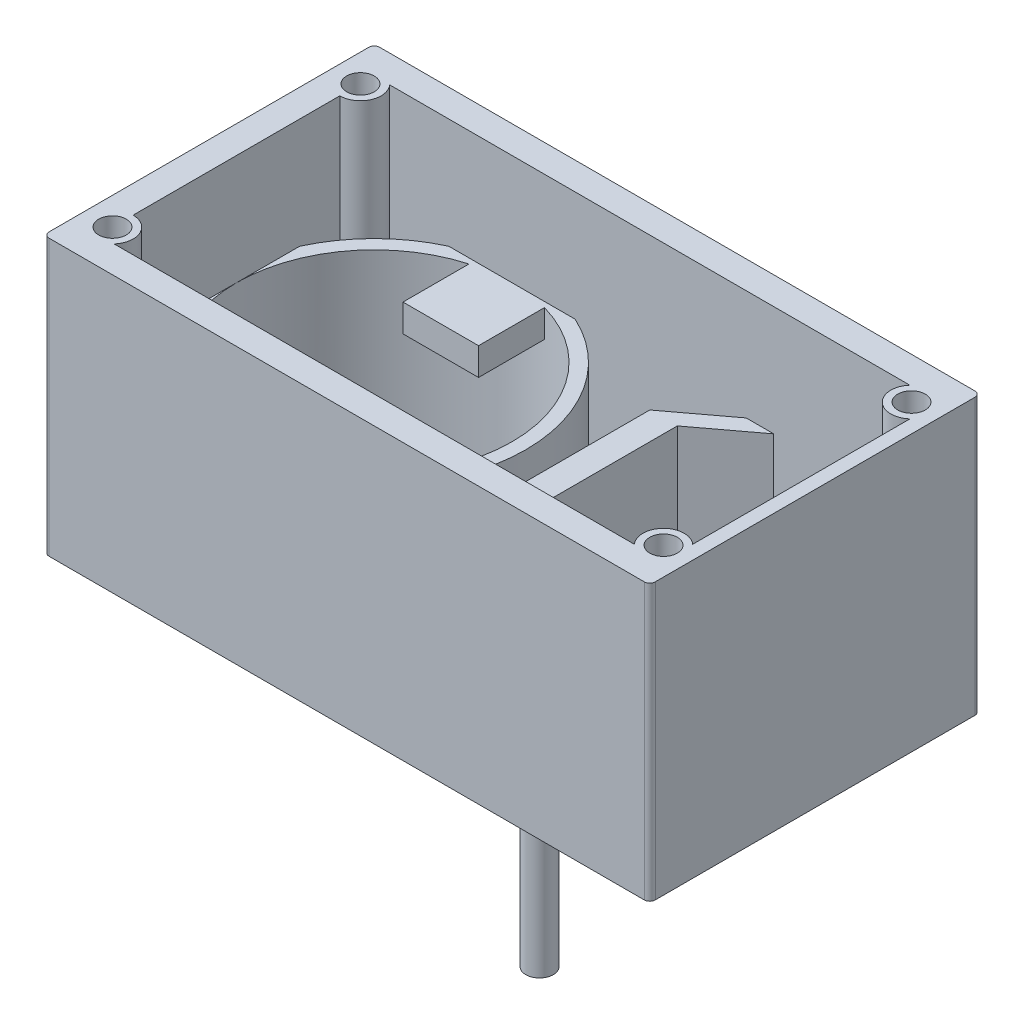
SolidWorks part; units mm, degrees
ref_plane "Front Plane" through (0, 0, 0) normal (0, 0, 1) x (1, 0, 0)
ref_plane "Top Plane" through (0, 0, 0) normal (0, 1, 0) x (1, 0, 0)
ref_plane "Right Plane" through (0, 0, 0) normal (1, 0, 0) x (0, 0, -1)
sketch "Sketch1" plane through (0, 0, 0) normal (0, 1, 0) x (1, 0, 0)
  line L1 (-11, -6) -> (11, -6)
  line L2 (-11, -6) -> (-11, 6)
  line L3 (-11, 6) -> (11, 6)
  line L4 (11, -6) -> (11, 6)
  line L5 (-11, -6) -> (11, 6) construction
  line L6 (-11, 6) -> (11, -6) construction
  point P0 (0, 0)
  dimension "D1" = 12
  dimension "D2" = 22
extrude "Boss-Extrude1" add sketch "Sketch1" along normal blind 10
sketch "Sketch2" plane through (0, 10, 0) normal (0, 1, 0) x (1, 0, 0)
  line L0 (11, 6) -> (-11, 6) construction
  line L1 (10.5, -5) -> (-10, -5)
  line L2 (10.5, -5) -> (10.5, 5)
  line L3 (10.5, 5) -> (-10, 5)
  line L4 (-10, -5) -> (-10, 5)
  line L5 (10.5, -5) -> (-10, 5) construction
  line L6 (10.5, 5) -> (-10, -5) construction
  line L7 (11, -6) -> (11, 6) construction
  point P0 (0.25, 0)
  dimension "D1" = 20.5
  dimension "D2" = 10
  dimension "D3" = 1
  dimension "D4" = 0.5
extrude "Cut-Extrude1" cut sketch "Sketch2" against normal blind 9 contours L4 L3 L2 L1
fillet "Fillet1" radius 0.2 4 edges at (-11, 5, -6) (11, 5, -6) (11, 5, 6) (-11, 5, 6)
sketch "Sketch3" plane through (0, 0, 0) normal (0, -1, 0) x (-1, 0, 0)
  circle A0 centre (5, 0) radius 5
extrude "Cut-Extrude2" cut sketch "Sketch3" against normal through all
sketch "Sketch4" plane through (0, 0, 0) normal (0, -1, 0) x (-1, 0, 0)
  circle A0 centre (-1, 0) radius 0.5
extrude "Cut-Extrude3" cut sketch "Sketch4" against normal through all
sketch "Sketch5" plane through (0, 0, 0) normal (0, -1, 0) x (-1, 0, 0)
  line L0 (-10.5, -5) -> (-10.5, 5) construction
  circle A0 centre (-6.5, 0) radius 2
  dimension "D1" = 4
extrude "Cut-Extrude4" cut sketch "Sketch5" against normal through all
sketch "Sketch6" plane through (0, 1, 0) normal (0, 1, 0) x (1, 0, 0)
  line L0 (2.5, 9.9437) -> (2.5, -10.995) construction
  line L1 (10.5, -5) -> (10.5, 5) construction
  line L2 (-14.9978, 3.5) -> (28.4787, 3.5) construction
  line L3 (20.7123, -3.5) -> (-19.3378, -3.5) construction
  line L4 (0, 0) -> (34.8745, 0) construction
  line L5 (1.5, 9.9437) -> (1.5, -10.995) construction
  line L6 (4.5, 12.7723) -> (4.5, -14.9146) construction
  line L7 (3.5, 10.9096) -> (3.5, -15.2533) construction
  line L8 (2.5, -3.5) -> (2.5, 3.5)
  line L9 (2.5, 3.5) -> (4.5, 5)
  line L10 (10.5, 5) -> (-5, 5) construction
  line L11 (4.5, 5) -> (3.5, 5)
  line L12 (3.5, 5) -> (1.5, 3.5)
  line L13 (1.5, 3.5) -> (1.5, -3.5)
  line L14 (1.5, -3.5) -> (3.5, -5)
  line L15 (10.5, -5) -> (-5, -5) construction
  line L16 (3.5, -5) -> (4.5, -5)
  line L17 (4.5, -5) -> (2.5, -3.5)
  dimension "D1" = 8
  dimension "D2" = 3.5
  dimension "D3" = 3.5
  dimension "D4" = 1
  dimension "D5" = 2
  dimension "D6" = 1
extrude "Boss-Extrude2" add sketch "Sketch6" along normal blind 5
sketch "Sketch9" plane through (0, 1, 0) normal (0, 1, 0) x (1, 0, 0)
  circle A0 centre (-5, 0) radius 5.5
  circle A1 centre (-5, 0) radius 5
extrude "Boss-Extrude3" add sketch "Sketch9" along normal blind 5
sketch "Sketch10" plane through (0, 1, 0) normal (0, 1, 0) x (1, 0, 0)
  circle A0 centre (1, 0) radius 1
  circle A1 centre (1, 0) radius 0.5
extrude "Boss-Extrude4" add sketch "Sketch10" along normal blind 2
sketch "Sketch12" plane through (0, 3, 0) normal (0, 1, 0) x (1, 0, 0)
  circle A0 centre (1, 0) radius 0.5
extrude "Boss-Extrude6" add sketch "Sketch12" against normal blind 1
sketch "Sketch13" plane through (0, 1, 0) normal (0, 1, 0) x (1, 0, 0)
  circle A0 centre (10, 4.5) radius 0.75
  circle A1 centre (10, 4.5) radius 0.5
extrude "Boss-Extrude7" add sketch "Sketch13" along normal blind 9
sketch "Sketch14" plane through (0, 0, 0) normal (0, -1, 0) x (-1, 0, 0)
  circle A0 centre (-10, 4.5) radius 0.5
extrude "Cut-Extrude5" cut sketch "Sketch14" against normal through all
mirror "Mirror1" about plane through (0, 0, 0) normal (1, 0, 0) of "Cut-Extrude5", "Boss-Extrude7"
mirror "Mirror2" about plane through (0, 0, 0) normal (0, 0, 1) of "Mirror1"
sketch "Sketch15" plane through (0, 6, 0) normal (0, 1, 0) x (1, 0, 0)
  line L0 (-6.3706, 2.4148) -> (-6.3706, 5.5363)
  line L1 (-6.3706, -5.5363) -> (-3.6294, -5.5363)
  line L2 (-6.3706, -5.5363) -> (-6.3706, -2.4148)
  line L3 (-6.3706, 5.5363) -> (-3.6294, 5.5363)
  line L4 (-3.6294, -5.5363) -> (-3.6294, -2.4148)
  line L7 (-6.3706, -2.4148) -> (-3.6294, -2.4148)
  line L9 (-6.3706, 2.4148) -> (-3.6294, 2.4148)
  line L15 (-3.6294, 2.4148) -> (-3.6294, 5.5363)
  point P0 (-5, 0)
  point P1 (-5, 0)
  point P9 (-5, 0)
extrude "Boss-Extrude8" add sketch "Sketch15" against normal blind 1
sketch "Sketch16" plane through (0, 0, 0) normal (0, -1, 0) x (1, 0, 0)
  circle A0 centre (1, 0) radius 0.5
extrude "Boss-Extrude9" add sketch "Sketch16" along normal blind 10 separate body
